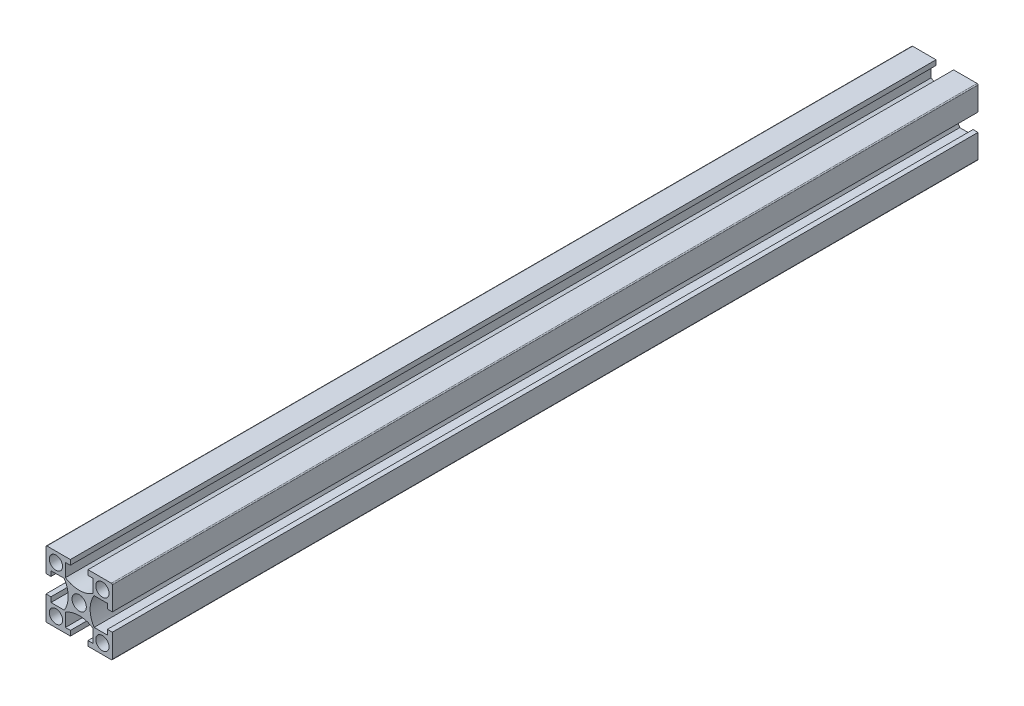
SolidWorks part; units mm, degrees
ref_plane "정면" through (0, 0, 0) normal (0, 0, 1) x (1, 0, 0)
ref_plane "윗면" through (0, 0, 0) normal (0, 1, 0) x (1, 0, 0)
ref_plane "우측면" through (0, 0, 0) normal (1, 0, 0) x (0, 0, -1)
sketch "스케치1" plane through (0, 0, 0) normal (0, 0, 1) x (1, 0, 0)
  line L0 (0, 32.0265) -> (0, -31.6588) construction
  line L1 (-10, 10) -> (-10, -10)
  line L2 (-10, 10) -> (10, 10)
  line L3 (-10, 2.65) -> (-8.5, 2.65)
  line L4 (13.6618, 0) -> (-11.6993, 0) construction
  line L5 (-8.5, 2.65) -> (-8.5, 4.15)
  line L6 (-8.5, 4.15) -> (-4.5032, 4.15)
  line L7 (-10, -2.65) -> (-8.5, -2.65)
  line L8 (-8.5, -2.65) -> (-8.5, -4.15)
  line L9 (-8.5, -4.15) -> (-4.5032, -4.15)
  line L10 (-10, -10) -> (10, -10)
  line L11 (10, 10) -> (10, -10)
  circle A0 centre (-7, 7) radius 2
  circle A1 centre (-7, -7) radius 2
  arc A2 (-4.5032, 4.15) -> (-4.5032, -4.15) centre (-11.0587, 0) cw
  circle A3 centre (0, 0) radius 2.15
  circle A4 centre (7, 7) radius 2
  circle A5 centre (7, -7) radius 2
  point P21 (-10, 0)
  point P23 (-3.3, 0)
  point P31 (0, -10)
  point P32 (0, 10)
  dimension "D3" = 4
  dimension "D9" = 6.7
  dimension "D10" = 4.3
  dimension "D11" = 7.7587
  dimension "D1" = 20
  dimension "D2" = 20
  dimension "D4" = 14
  dimension "D5" = 14
  dimension "D6" = 5.3
  dimension "D7" = 8.3
  dimension "D8" = 1.5
extrude "보스-돌출1" add sketch "스케치1" along normal blind 261 contours A0 | A4 | A3 | A5 | A1 | A2 L6 L5 L3 L1 L7 L8 L9 | L2 L11 L10 L1 region at (-6.6069, 0, 0) region at (-7, 7, 0) region at (-7, -7, 0) region at (0, 0, 0) region at (7, 7, 0) region at (7, -7, 0)
extrude "컷-돌출1" cut sketch "스케치1<3>" along normal up to next contours A2 L6 L5 L3 L1 L7 L8 L9 region at (-6.6069, 0, 0)
sketch "스케치1<3>" plane through (0, 0, 0) normal (0, 0, 1) x (1, 0, 0) same geometry as "스케치1"
pattern_circular "원형 패턴1" count 4 over 360 about axis through (0, 0, 261) along (0, 0, -1) of "컷-돌출1" reverse direction yes
fillet "필렛1" radius 0.3 4 edges at (10, -10, 130.5) (-10, -10, 130.5) (-10, 10, 130.5) (10, 10, 130.5)
